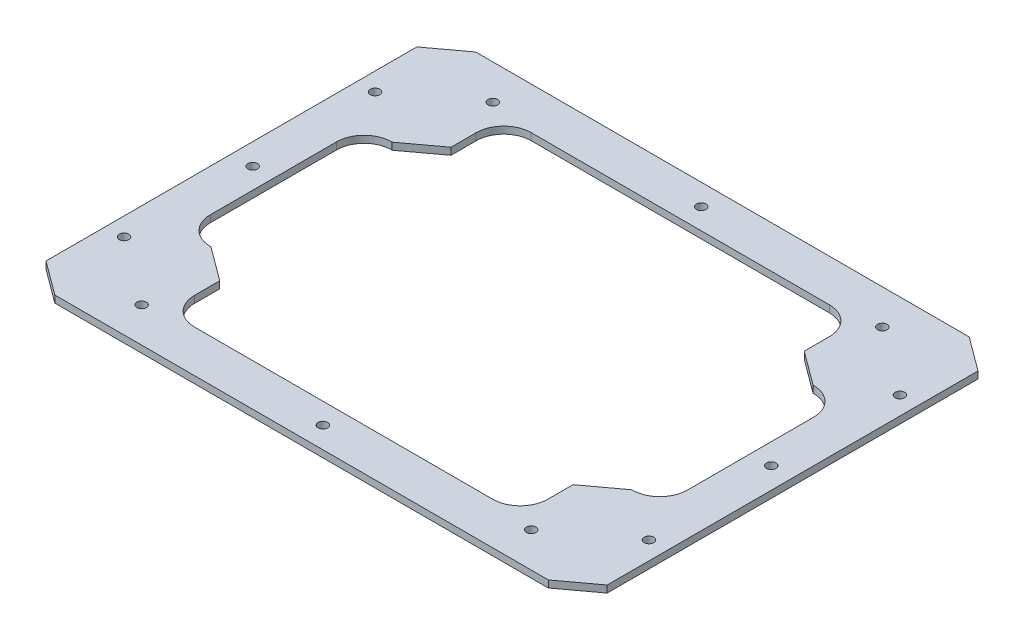
SolidWorks part; units mm, degrees
material "Thornel Mat VMA"
ref_plane "Front Plane" through (0, 0, 0) normal (0, 0, 1) x (1, 0, 0)
ref_plane "Top Plane" through (0, 0, 0) normal (0, 1, 0) x (1, 0, 0)
ref_plane "Right Plane" through (0, 0, 0) normal (1, 0, 0) x (0, 0, -1)
sketch "Sketch1" plane through (0, 0, 0) normal (0, 1, 0) x (1, 0, 0)
  line L0 (-127, 83.9186) -> (-111.6865, 95.25)
  line L1 (-127, -95.25) -> (127, -95.25)
  line L2 (-127, -95.25) -> (-127, 95.25)
  line L3 (-127, 95.25) -> (127, 95.25)
  line L4 (127, -95.25) -> (127, 95.25)
  line L5 (-107.95, 28.565) -> (-107.95, -28.565)
  line L8 (-95.504, 41.011) -> (-95.25, 41.011)
  line L10 (-127, 95.25) -> (127, -95.25) construction
  line L12 (127, 83.9186) -> (111.6865, 95.25)
  line L14 (79.9365, 52.3423) -> (79.9365, 63.754)
  line L15 (95.25, 41.011) -> (79.9365, 52.3423)
  line L16 (95.504, 41.011) -> (95.25, 41.011)
  line L17 (107.95, 28.565) -> (107.95, -28.565)
  line L18 (127, -83.9186) -> (111.6865, -95.25)
  line L19 (95.504, -41.011) -> (95.25, -41.011)
  line L20 (95.25, -41.011) -> (79.9365, -52.3423)
  line L21 (79.9365, -52.3423) -> (79.9365, -63.754)
  line L22 (127, 0) -> (-127, 0) construction
  line L23 (0, -13.6985) -> (0, 95.25) construction
  line L26 (-79.9365, -52.3423) -> (-79.9365, -63.754)
  line L27 (-95.25, 41.011) -> (-127, 83.9186) construction
  line L28 (-95.25, 41.011) -> (-79.9365, 52.3423)
  line L29 (-79.9365, 52.3423) -> (-79.9365, 63.754)
  line L31 (-95.25, -41.011) -> (-79.9365, -52.3423)
  line L32 (-95.504, -41.011) -> (-95.25, -41.011)
  line L33 (-127, -83.9186) -> (-111.6865, -95.25)
  line L34 (-79.9365, 52.3423) -> (-111.6865, 95.25) construction
  line L36 (-67.4905, 76.2) -> (79.9365, 76.2)
  line L37 (38.8318, 76.2) -> (67.4905, 76.2)
  line L38 (-67.4905, -76.2) -> (79.9365, -76.2)
  line L39 (38.1, -76.2) -> (67.4905, -76.2)
  arc A0 (-79.9365, 63.754) -> (-67.4905, 76.2) centre (-67.4905, 63.754) cw
  arc A1 (-107.95, 28.565) -> (-95.504, 41.011) centre (-95.504, 28.565) cw
  arc A2 (-95.504, -41.011) -> (-107.95, -28.565) centre (-95.504, -28.565) cw
  arc A3 (-67.4905, -76.2) -> (-79.9365, -63.754) centre (-67.4905, -63.754) cw
  arc A4 (79.9365, -63.754) -> (67.4905, -76.2) centre (67.4905, -63.754) cw
  arc A5 (79.9365, 63.754) -> (67.4905, 76.2) centre (67.4905, 63.754) ccw
  arc A6 (95.504, 41.011) -> (107.95, 28.565) centre (95.504, 28.565) cw
  arc A7 (95.504, -41.011) -> (107.95, -28.565) centre (95.504, -28.565) ccw
  point P0 (0, 0)
  point P1 (0, 0)
  point P14 (0, 0)
  point P22 (0, 76.2)
  point P33 (107.95, 0)
  point P35 (-79.9365, 76.2)
  point P41 (0, 0)
  point P44 (-107.95, 0)
  point P45 (-38.1, 0)
  point P46 (-31.75, 0)
  point P51 (-107.95, 41.011)
  point P54 (-107.95, -41.011)
  point P57 (-79.9365, -76.2)
  point P60 (79.9365, -76.2)
  point P63 (79.9365, 76.2)
  point P66 (107.95, 41.011)
  point P69 (107.95, -41.011)
  dimension "D8" = 12.446
  dimension "D1" = 190.5
  dimension "D2" = 254
  dimension "D3" = 19.05
  dimension "D4" = 19.05
  dimension "D5" = 143.5
  dimension "D6" = 19.05
  dimension "D7" = 12.7
extrude "Boss-Extrude1" add sketch "Sketch1" along normal blind 3.175 contours L2 L1 L4 L3 L8 region at (-117.4547, 0, -87.0321)
sketch "Sketch2" plane through (0, 3.175, 0) normal (0, 1, 0) x (1, 0, 0)
  line L0 (-87.5933, 46.6767) -> (-119.3433, 89.5843) construction
  line L1 (-95.25, 41.011) -> (-79.9365, 52.3423) construction
  line L2 (-127, 83.9186) -> (-111.6865, 95.25) construction
  line L3 (0, 0) -> (0, 95.25) construction
  line L4 (-111.6865, 95.25) -> (111.6865, 95.25) construction
  line L5 (0, 0) -> (-127, 0) construction
  line L6 (-127, -83.9186) -> (-127, 83.9186) construction
  line L7 (-103.4683, 68.1305) -> (-88.1548, 79.4619) construction
  line L8 (127, -83.9186) -> (127, 83.9186) construction
  line L9 (-111.6865, -95.25) -> (111.6865, -95.25) construction
  circle A0 centre (-88.1548, 79.4619) radius 2.159
  circle A1 centre (88.1548, 79.4619) radius 2.159
  circle A2 centre (88.1548, -79.4619) radius 2.159
  circle A3 centre (-88.1548, -79.4619) radius 2.159
  circle A4 centre (-118.7817, 56.7991) radius 2.159
  circle A5 centre (118.7817, 56.7991) radius 2.159
  circle A6 centre (-118.7817, -56.7991) radius 2.159
  circle A7 centre (118.7817, -56.7991) radius 2.159
  circle A8 centre (0, -85.598) radius 2.159
  circle A9 centre (0, 85.598) radius 2.159
  circle A10 centre (-117.348, -0.0205) radius 2.159
  circle A11 centre (117.348, -0.0205) radius 2.159
  point P35 (0, 0)
  dimension "D2" = 4.318
  dimension "D3" = 9.652
  dimension "D1" = 19.05
  dimension "D4" = 9.652
  dimension "D5" = 127
  dimension "D6" = 127
  dimension "D7" = 127
extrude "Cut-Extrude1" cut sketch "Sketch2" against normal through all
